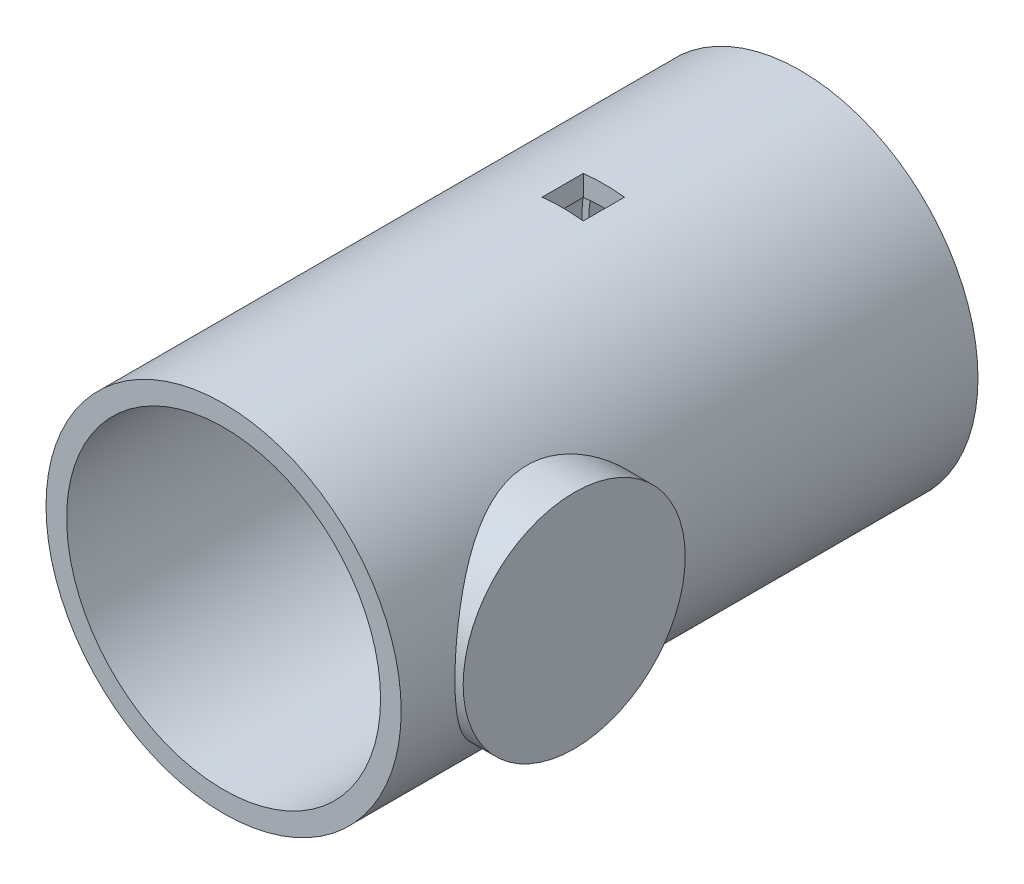
SolidWorks part; units mm, degrees
ref_plane "Front Plane" through (0, 0, 0) normal (0, 0, 1) x (1, 0, 0)
ref_plane "Top Plane" through (0, 0, 0) normal (0, 1, 0) x (1, 0, 0)
ref_plane "Right Plane" through (0, 0, 0) normal (1, 0, 0) x (0, 0, -1)
sketch "Sketch1" plane through (0, 0, 0) normal (0, 0, 1) x (1, 0, 0)
  circle A1 centre (0, 0) radius 43.1
  dimension "D1" = 86.2
extrude "Boss-Extrude1" add sketch "Sketch1" along normal blind 140
ref_plane "Plane1" through (0, 43.1, 0) normal (0, 1, 0) x (1, 0, 0)
sketch "Sketch6" plane through (0, 43.1, 0) normal (0, 1, 0) x (1, 0, 0)
  line L2 (-5, -57.7) -> (5, -57.7)
  line L3 (-5, -57.7) -> (-5, -47.7)
  line L4 (-5, -47.7) -> (5, -47.7)
  line L5 (5, -57.7) -> (5, -47.7)
  line L6 (-5, -57.7) -> (5, -47.7) construction
  line L7 (-5, -47.7) -> (5, -57.7) construction
  point P2 (0, -52.7)
  dimension "D2" = 10
  dimension "D1" = 52.7
  dimension "D3" = 10
extrude "Cut-Extrude3" cut sketch "Sketch6" against normal through all
ref_plane "Plane2" through (45.1, 0, 0) normal (1, 0, 0) x (0, 0, -1)
sketch "Sketch8" plane through (45.1, 0, 0) normal (1, 0, 0) x (0, 0, -1)
  circle A0 centre (-100, 0) radius 26.95
  dimension "D1" = 53.9
  dimension "D2" = 100
extrude "Boss-Extrude2" add sketch "Sketch8" against normal blind 20
mirror "Mirror1" [suppressed] about plane through (0, 0, 0) normal (1, 0, 0)
sketch "Sketch5" plane through (0, 0, 140) normal (0, 0, 1) x (1, 0, 0)
  circle A0 centre (0, 0) radius 31.75
  dimension "D1" = 63.5
sketch "Sketch2" plane through (0, 0, 140) normal (0, 0, 1) x (1, 0, 0)
  circle A0 centre (0, 0) radius 38.1
  dimension "D1" = 76.2
extrude "Cut-Extrude4" cut sketch "Sketch5" against normal through all
extrude "Cut-Extrude5" cut sketch "Sketch2" against normal blind 135
sketch "Sketch9" plane through (0, 0, 5) normal (0, 0, 1) x (1, 0, 0)
  circle A0 centre (0, 0) radius 38.1
  circle A1 centre (0, 0) radius 36.44
  dimension "D1" = 76.2
  dimension "D2" = 1.66
extrude "Boss-Extrude3" add sketch "Sketch9" along normal blind 10
